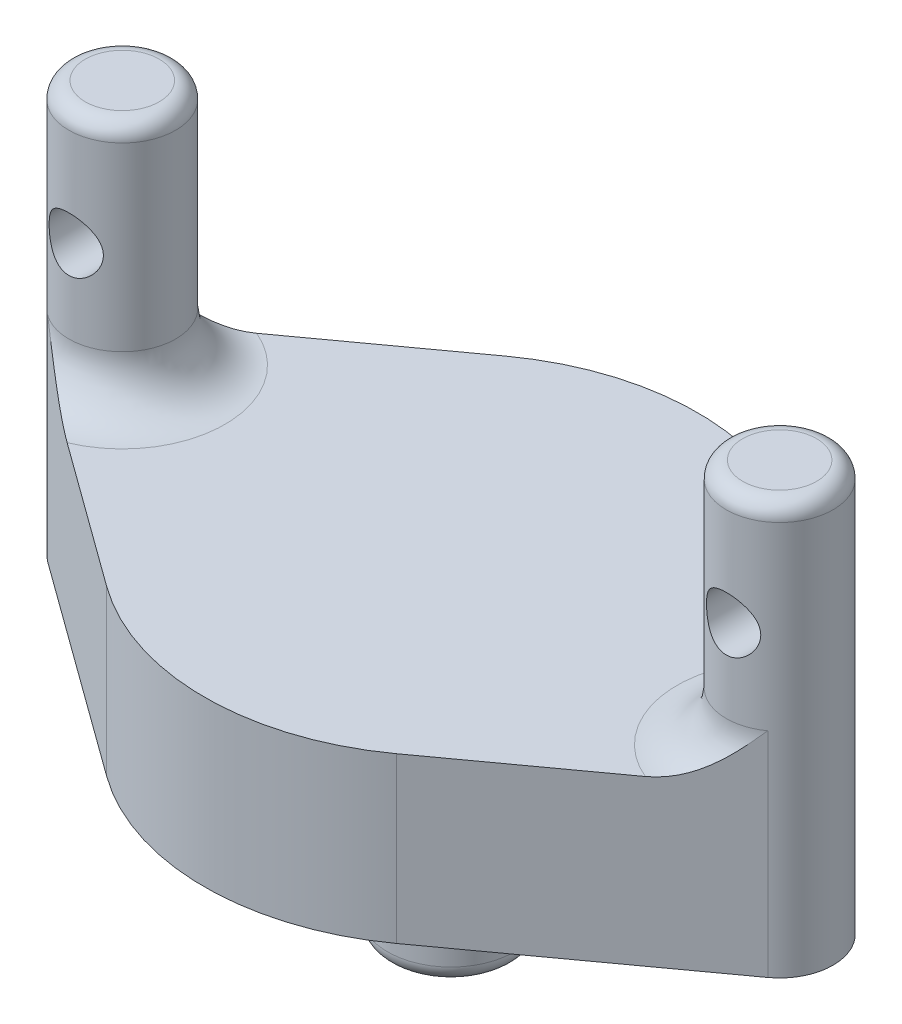
SolidWorks part; units mm, degrees
ref_plane "Front Plane" through (0, 0, 0) normal (0, 0, 1) x (1, 0, 0)
ref_plane "Top Plane" through (0, 0, 0) normal (0, 1, 0) x (1, 0, 0)
ref_plane "Right Plane" through (0, 0, 0) normal (1, 0, 0) x (0, 0, -1)
sketch "Sketch1" plane through (0, 0, 0) normal (0, 1, 0) x (1, 0, 0)
  line L0 (-20, 0) -> (20, 0) construction
  circle A0 centre (-20, 0) radius 3.25
  circle A1 centre (20, 0) radius 3.25
  dimension "D1" = 6.5
  dimension "D2" = 40
extrude "Boss-Extrude1" add sketch "Sketch1" along normal blind 15
sketch "Sketch2" plane through (0, 0, 0) normal (0, -1, 0) x (1, 0, 0)
  line L0 (-21.9094, 2.63) -> (-8.8125, 12.1384)
  line L1 (0, 15) -> (0, -15) construction
  line L2 (-8.8125, -12.1384) -> (-21.9094, -2.63)
  line L3 (8.8125, -12.1384) -> (21.9094, -2.63)
  line L4 (21.9094, 2.63) -> (8.8125, 12.1384)
  arc A0 (-21.9094, 2.63) -> (-21.9094, -2.63) centre (-20, 0) ccw
  arc A2 (8.8125, 12.1384) -> (-8.8125, 12.1384) centre (0, 0) ccw
  arc A4 (-8.8125, -12.1384) -> (8.8125, -12.1384) centre (0, 0) ccw
  circle A5 centre (-20, 0) radius 3.25 construction
  arc A6 (21.9094, 2.63) -> (21.9094, -2.63) centre (20, 0) cw
  dimension "D2" = 15
extrude "Boss-Extrude2" add sketch "Sketch2" along normal blind 10
sketch "Sketch3" plane through (0, -10, 0) normal (0, -1, 0) x (1, 0, 0)
  circle A0 centre (0, 0) radius 3.85
  dimension "D1" = 7.7
extrude "Boss-Extrude3" add sketch "Sketch3" along normal blind 10
fillet "Fillet2" radius 1 1 edges at (0, -10, -3.85)
fillet "Fillet1" radius 1 3 edges at (-20, 15, 3.25) (0, -20, -3.85) (20, 15, 3.25)
fillet "Fillet3" radius 3 2 edges at (16.75, 0, 0)
sketch "Sketch4" plane through (0, 0, 0) normal (0, 0, 1) x (1, 0, 0)
  line L0 (-20, 15) -> (-20, 3) construction
  line L1 (-17.75, 15) -> (-22.25, 15) construction
  line L2 (-16.75, 3) -> (-21.9094, 3) construction
  line L3 (0, 0) -> (0, 15) construction
  circle A0 centre (-20, 8) radius 1.65
  circle A1 centre (20, 8) radius 1.65
  dimension "D1" = 3.3
  dimension "D2" = 7
extrude "Cut-Extrude1" cut sketch "Sketch4" against normal through all and the other way through all
